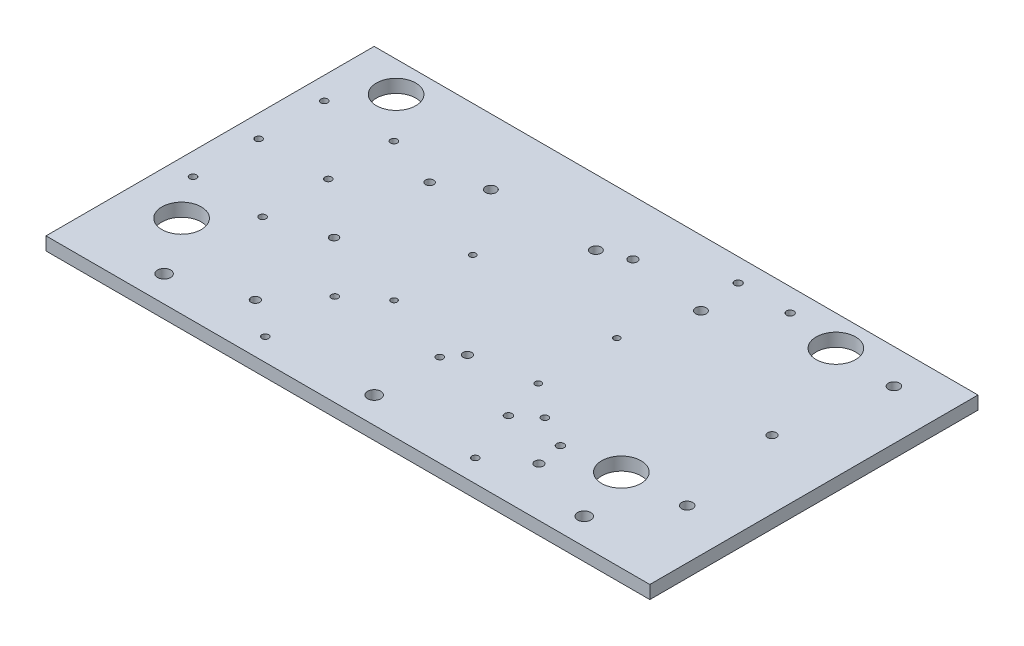
SolidWorks part; units mm, degrees
ref_plane "Front Plane" through (0, 0, 0) normal (0, 0, 1) x (1, 0, 0)
ref_plane "Top Plane" through (0, 0, 0) normal (0, 1, 0) x (1, 0, 0)
ref_plane "Right Plane" through (0, 0, 0) normal (1, 0, 0) x (0, 0, -1)
sketch "Sketch1" plane through (0, 0, 0) normal (0, 1, 0) x (1, 0, 0)
  line L1 (0, 0) -> (292.1, 0)
  line L2 (0, 0) -> (0, 158.75)
  line L3 (0, 158.75) -> (292.1, 158.75)
  line L4 (292.1, 0) -> (292.1, 158.75)
  dimension "D1" = 292.1
  dimension "D2" = 158.75
extrude "Boss-Extrude1" add sketch "Sketch1" along normal blind 6.35
sketch "Sketch2" plane through (0, 6.35, 0) normal (0, 1, 0) x (1, 0, 0)
  line L0 (0, 25.4) -> (292.1, 25.4) construction
  line L1 (0, 12.7) -> (292.1, 12.7) construction
  line L2 (146.05, 0) -> (146.05, 158.75) construction
  line L4 (0, 158.75) -> (0, 0)
  line L5 (0, 0) -> (292.1, 0)
  line L6 (292.1, 0) -> (292.1, 158.75)
  line L7 (292.1, 158.75) -> (0, 158.75)
  line L8 (0, 158.75) -> (0, 0) construction
  line L9 (0, 0) -> (292.1, 0) construction
  line L10 (292.1, 0) -> (292.1, 158.75) construction
  line L11 (292.1, 158.75) -> (0, 158.75) construction
  circle A0 centre (146.05, 12.7) radius 3.175
  circle A1 centre (247.65, 12.7) radius 3.175
  circle A2 centre (44.45, 12.7) radius 3.175
  dimension "D6" = 6.35
  dimension "D7" = 6.35
  dimension "D8" = 6.35
  dimension "D2" = 25.4
  dimension "D3" = 12.7
  dimension "D4" = 101.6
  dimension "D5" = 101.6
extrude "Cut-Extrude2" cut sketch "Sketch2" against normal blind 6.35
sketch "Sketch5" [suppressed] plane through (0, 6.35, 0) normal (0, 1, 0) x (1, 0, 0)
  line L0 (0, 0) -> (292.1, 0) construction
  line L1 (279.4, 31.75) -> (143.9, 31.75) construction
  line L2 (279.4, 31.75) -> (279.4, 75.25) construction
  line L3 (279.4, 75.25) -> (143.9, 75.25) construction
  line L4 (143.9, 31.75) -> (143.9, 75.25) construction
  line L5 (292.1, 0) -> (292.1, 158.75) construction
  circle A0 centre (279.4, 31.75) radius 1.525
  circle A1 centre (279.4, 75.25) radius 1.525
  circle A2 centre (143.9, 75.25) radius 1.525
  circle A3 centre (143.9, 31.75) radius 1.525
  dimension "D3" = 3.05
  dimension "D1" = 43.5
  dimension "D2" = 135.5
  dimension "D4" = 31.75
  dimension "D5" = 12.7
sketch "Sketch6" plane through (0, 6.35, 0) normal (0, 1, 0) x (1, 0, 0)
  line L0 (238.125, 158.75) -> (238.125, 0) construction
  line L1 (292.1, 158.75) -> (0, 158.75) construction
  line L2 (0, 0) -> (292.1, 0) construction
  line L4 (146.05, 158.75) -> (146.05, 0) construction
  line L5 (0, 25.4) -> (292.1, 25.4) construction
  line L6 (0, 158.75) -> (0, 0) construction
  line L7 (292.1, 0) -> (292.1, 158.75) construction
  line L8 (25.4, 40.1879) -> (238.125, 40.1879) construction
  line L9 (25.4, 143.9621) -> (238.125, 143.9621) construction
  line L10 (0, 92.075) -> (292.1, 92.075) construction
  line L11 (0, 158.75) -> (0, 25.4) construction
  line L12 (25.4, 143.9621) -> (25.4, 92.075) construction
  line L13 (25.4, 92.075) -> (25.4, 40.1879) construction
  circle A0 centre (25.4, 40.1879) radius 9.525
  circle A1 centre (238.125, 40.1879) radius 9.525
  circle A2 centre (25.4, 143.9621) radius 9.525
  circle A3 centre (238.125, 143.9621) radius 9.525
  dimension "D2" = 19.05
  dimension "D3" = 19.05
  dimension "D1" = 25.4
  dimension "D4" = 25.4
  dimension "D5" = 53.975
extrude "Cut-Extrude3" cut sketch "Sketch6" against normal through all
sketch "Sketch8" plane through (0, 6.35, 0) normal (0, 1, 0) x (1, 0, 0)
  line L0 (265.43, 121.908) -> (265.43, 112.242) construction
  line L1 (270.764, 112.242) -> (270.764, 121.908) construction
  line L2 (265.43, 96.908) -> (265.43, 87.242)
  line L3 (270.764, 87.242) -> (270.764, 96.908)
  line L4 (265.43, 96.908) -> (265.43, 87.242) construction
  line L5 (270.764, 87.242) -> (270.764, 96.908) construction
  line L6 (265.43, 146.908) -> (265.43, 137.242) construction
  line L7 (270.764, 137.242) -> (270.764, 146.908) construction
  line L8 (265.43, 96.908) -> (265.43, 87.242) construction
  line L9 (270.764, 87.242) -> (270.764, 96.908) construction
  line L10 (265.43, 121.908) -> (265.43, 112.242) construction
  line L11 (270.764, 112.242) -> (270.764, 121.908) construction
  line L12 (265.43, 71.908) -> (265.43, 62.242) construction
  line L13 (270.764, 62.242) -> (270.764, 71.908) construction
  line L14 (265.43, 96.908) -> (265.43, 87.242) construction
  line L15 (270.764, 87.242) -> (270.764, 96.908) construction
  line L16 (265.43, 71.908) -> (265.43, 62.242) construction
  line L17 (270.764, 62.242) -> (270.764, 71.908) construction
  line L18 (265.43, 46.908) -> (265.43, 37.242) construction
  line L19 (270.764, 37.242) -> (270.764, 46.908) construction
  line L20 (265.43, 96.908) -> (265.43, 121.908) construction
  line L21 (268.097, 137.242) -> (268.097, 146.908) construction
  line L22 (268.097, 37.242) -> (268.097, 46.908) construction
  line L23 (143.764, 129.54) -> (134.239, 129.54) construction
  line L24 (134.239, 124.46) -> (143.764, 124.46) construction
  line L25 (213.1283, 38.3159) -> (211.5027, 38.3159)
  line L26 (211.5027, 34.7345) -> (213.1283, 34.7345)
  line L27 (222.285, 31.6611) -> (222.285, 152.4889)
  line L28 (222.285, 152.4889) -> (177.2, 152.4889)
  line L29 (177.2, 152.4889) -> (177.2, 31.6611)
  line L30 (177.2, 31.6611) -> (222.285, 31.6611)
  line L31 (222.285, 31.6611) -> (222.285, 152.4889) construction
  line L32 (222.285, 152.4889) -> (177.2, 152.4889) construction
  line L33 (177.2, 152.4889) -> (177.2, 31.6611) construction
  line L34 (177.2, 31.6611) -> (222.285, 31.6611) construction
  line L35 (213.1283, 38.3159) -> (211.5027, 38.3159) construction
  line L36 (211.5027, 34.7345) -> (213.1283, 34.7345) construction
  line L37 (187.9823, 38.3159) -> (186.3567, 38.3159)
  line L38 (186.3567, 34.7345) -> (187.9823, 34.7345)
  line L39 (187.9823, 38.3159) -> (186.3567, 38.3159) construction
  line L40 (186.3567, 34.7345) -> (187.9823, 34.7345) construction
  line L41 (211.5027, 145.8341) -> (213.1283, 145.8341)
  line L42 (213.1283, 149.4155) -> (211.5027, 149.4155)
  line L43 (211.5027, 145.8341) -> (213.1283, 145.8341) construction
  line L44 (213.1283, 149.4155) -> (211.5027, 149.4155) construction
  line L45 (186.3567, 145.8341) -> (187.9823, 145.8341)
  line L46 (187.9823, 149.4155) -> (186.3567, 149.4155)
  line L47 (186.3567, 145.8341) -> (187.9823, 145.8341) construction
  line L48 (187.9823, 149.4155) -> (186.3567, 149.4155) construction
  line L49 (194.564, 129.54) -> (185.039, 129.54)
  line L50 (185.039, 124.46) -> (194.564, 124.46)
  line L51 (194.564, 129.54) -> (185.039, 129.54) construction
  line L52 (185.039, 124.46) -> (194.564, 124.46) construction
  line L53 (92.964, 129.54) -> (83.439, 129.54) construction
  line L54 (83.439, 124.46) -> (92.964, 124.46) construction
  line L55 (194.564, 129.54) -> (143.764, 129.54) construction
  line L56 (83.439, 127) -> (194.564, 127) construction
  line L57 (189.8015, 124.46) -> (189.8015, 129.54) construction
  line L58 (88.2015, 124.46) -> (88.2015, 129.54) construction
  line L63 (109.05, 54.7) -> (183.05, 54.7)
  line L64 (183.05, 54.7) -> (183.05, 97.7)
  line L65 (183.05, 97.7) -> (109.05, 97.7)
  line L66 (109.05, 97.7) -> (109.05, 54.7)
  line L67 (109.05, 54.7) -> (183.05, 54.7) construction
  line L68 (183.05, 54.7) -> (183.05, 97.7) construction
  line L69 (183.05, 97.7) -> (109.05, 97.7) construction
  line L70 (109.05, 97.7) -> (109.05, 54.7) construction
  line L82 (186.3567, 36.5252) -> (187.9823, 36.5252) construction
  line L83 (211.5027, 36.5252) -> (213.1283, 36.5252) construction
  line L84 (211.5027, 147.6248) -> (213.1283, 147.6248) construction
  line L85 (186.3567, 147.6248) -> (187.9823, 147.6248) construction
  line L88 (70.3882, 66.9707) -> (81.4118, 66.9707)
  line L89 (81.4118, 70.9077) -> (70.3882, 70.9077)
  line L90 (70.3882, 66.9707) -> (81.4118, 66.9707) construction
  line L91 (81.4118, 70.9077) -> (70.3882, 70.9077) construction
  line L92 (77.8685, 63.0845) -> (77.8685, 68.9392)
  line L93 (73.9315, 68.9392) -> (73.9315, 63.0845)
  line L94 (126.4, 44.9707) -> (126.4, 139.1793)
  line L95 (25.4, 44.9707) -> (126.4, 44.9707)
  line L96 (25.4, 139.1793) -> (25.4, 44.9707)
  line L97 (126.4, 139.1793) -> (25.4, 139.1793)
  line L98 (126.4, 44.9707) -> (126.4, 139.1793) construction
  line L99 (25.4, 44.9707) -> (126.4, 44.9707) construction
  line L100 (25.4, 139.1793) -> (25.4, 44.9707) construction
  line L101 (126.4, 139.1793) -> (25.4, 139.1793) construction
  line L102 (77.8685, 63.0845) -> (77.8685, 68.9392) construction
  line L103 (73.9315, 68.9392) -> (73.9315, 63.0845) construction
  line L104 (73.9315, 115.2108) -> (73.9315, 109.3561)
  line L105 (77.8685, 109.3561) -> (77.8685, 115.2108)
  line L106 (73.9315, 115.2108) -> (73.9315, 109.3561) construction
  line L107 (77.8685, 109.3561) -> (77.8685, 115.2108) construction
  line L108 (70.3882, 113.2423) -> (81.4118, 113.2423)
  line L109 (81.4118, 117.1793) -> (70.3882, 117.1793)
  line L110 (70.3882, 113.2423) -> (81.4118, 113.2423) construction
  line L111 (81.4118, 117.1793) -> (70.3882, 117.1793) construction
  arc A0 (265.43, 112.242) -> (270.764, 112.242) centre (268.097, 112.242) ccw construction
  arc A1 (270.764, 121.908) -> (265.43, 121.908) centre (268.097, 121.908) ccw construction
  arc A2 (265.43, 87.242) -> (270.764, 87.242) centre (268.097, 87.242) ccw
  arc A3 (270.764, 96.908) -> (265.43, 96.908) centre (268.097, 96.908) ccw
  arc A4 (265.43, 87.242) -> (270.764, 87.242) centre (268.097, 87.242) ccw construction
  arc A5 (270.764, 96.908) -> (265.43, 96.908) centre (268.097, 96.908) ccw construction
  arc A6 (265.43, 137.242) -> (270.764, 137.242) centre (268.097, 137.242) ccw construction
  arc A7 (270.764, 146.908) -> (265.43, 146.908) centre (268.097, 146.908) ccw construction
  arc A8 (265.43, 87.242) -> (270.764, 87.242) centre (268.097, 87.242) ccw construction
  arc A9 (270.764, 96.908) -> (265.43, 96.908) centre (268.097, 96.908) ccw construction
  arc A10 (265.43, 112.242) -> (270.764, 112.242) centre (268.097, 112.242) ccw construction
  arc A11 (270.764, 121.908) -> (265.43, 121.908) centre (268.097, 121.908) ccw construction
  arc A12 (265.43, 62.242) -> (270.764, 62.242) centre (268.097, 62.242) ccw construction
  arc A13 (270.764, 71.908) -> (265.43, 71.908) centre (268.097, 71.908) ccw construction
  arc A14 (265.43, 87.242) -> (270.764, 87.242) centre (268.097, 87.242) ccw construction
  arc A15 (270.764, 96.908) -> (265.43, 96.908) centre (268.097, 96.908) ccw construction
  arc A16 (265.43, 62.242) -> (270.764, 62.242) centre (268.097, 62.242) ccw construction
  arc A17 (270.764, 71.908) -> (265.43, 71.908) centre (268.097, 71.908) ccw construction
  arc A18 (265.43, 37.242) -> (270.764, 37.242) centre (268.097, 37.242) ccw construction
  arc A19 (270.764, 46.908) -> (265.43, 46.908) centre (268.097, 46.908) ccw construction
  circle A20 centre (268.097, 42.075) radius 2.667
  circle A21 centre (268.097, 142.075) radius 2.667
  arc A22 (134.239, 129.54) -> (134.239, 124.46) centre (134.239, 127) ccw construction
  arc A23 (143.764, 124.46) -> (143.764, 129.54) centre (143.764, 127) ccw construction
  arc A24 (211.5027, 38.3159) -> (211.5027, 34.7345) centre (211.5027, 36.5252) ccw
  arc A25 (213.1283, 34.7345) -> (213.1283, 38.3159) centre (213.1283, 36.5252) ccw
  arc A26 (211.5027, 38.3159) -> (211.5027, 34.7345) centre (211.5027, 36.5252) ccw construction
  arc A27 (213.1283, 34.7345) -> (213.1283, 38.3159) centre (213.1283, 36.5252) ccw construction
  arc A28 (187.9823, 34.7345) -> (187.9823, 38.3159) centre (187.9823, 36.5252) ccw
  arc A29 (186.3567, 38.3159) -> (186.3567, 34.7345) centre (186.3567, 36.5252) ccw
  arc A30 (187.9823, 34.7345) -> (187.9823, 38.3159) centre (187.9823, 36.5252) ccw construction
  arc A31 (186.3567, 38.3159) -> (186.3567, 34.7345) centre (186.3567, 36.5252) ccw construction
  arc A32 (211.5027, 149.4155) -> (211.5027, 145.8341) centre (211.5027, 147.6248) ccw
  arc A33 (213.1283, 145.8341) -> (213.1283, 149.4155) centre (213.1283, 147.6248) ccw
  arc A34 (211.5027, 149.4155) -> (211.5027, 145.8341) centre (211.5027, 147.6248) ccw construction
  arc A35 (213.1283, 145.8341) -> (213.1283, 149.4155) centre (213.1283, 147.6248) ccw construction
  arc A36 (187.9823, 145.8341) -> (187.9823, 149.4155) centre (187.9823, 147.6248) ccw
  arc A37 (186.3567, 149.4155) -> (186.3567, 145.8341) centre (186.3567, 147.6248) ccw
  arc A38 (187.9823, 145.8341) -> (187.9823, 149.4155) centre (187.9823, 147.6248) ccw construction
  arc A39 (186.3567, 149.4155) -> (186.3567, 145.8341) centre (186.3567, 147.6248) ccw construction
  arc A40 (185.039, 129.54) -> (185.039, 124.46) centre (185.039, 127) ccw
  arc A41 (194.564, 124.46) -> (194.564, 129.54) centre (194.564, 127) ccw
  arc A42 (185.039, 129.54) -> (185.039, 124.46) centre (185.039, 127) ccw construction
  arc A43 (194.564, 124.46) -> (194.564, 129.54) centre (194.564, 127) ccw construction
  arc A44 (83.439, 129.54) -> (83.439, 124.46) centre (83.439, 127) ccw construction
  arc A45 (92.964, 124.46) -> (92.964, 129.54) centre (92.964, 127) ccw construction
  circle A46 centre (189.8015, 127) radius 2.54
  circle A47 centre (139.0015, 127) radius 2.54
  circle A48 centre (88.2015, 127) radius 2.54
  circle A50 centre (111.2, 57.2) radius 1.5
  circle A51 centre (111.2, 57.2) radius 1.5
  circle A52 centre (180.9, 57.2) radius 1.5
  circle A53 centre (180.9, 57.2) radius 1.5
  circle A54 centre (180.9, 95.2) radius 1.5
  circle A55 centre (180.9, 95.2) radius 1.5
  circle A56 centre (111.2, 95.2) radius 1.5
  circle A57 centre (111.2, 95.2) radius 1.5
  circle A58 centre (95.25, 10.795) radius 1.651
  circle A59 centre (95.25, 10.795) radius 1.651
  circle A60 centre (196.85, 10.795) radius 1.651
  circle A61 centre (196.85, 10.795) radius 1.651
  circle A62 centre (196.85, 44.45) radius 1.651
  circle A63 centre (196.85, 44.45) radius 1.651
  circle A64 centre (95.25, 44.45) radius 1.651
  circle A65 centre (95.25, 44.45) radius 1.651
  circle A66 centre (10.795, 123.825) radius 1.651
  circle A67 centre (10.795, 123.825) radius 1.651
  circle A68 centre (10.795, 60.325) radius 1.651
  circle A69 centre (10.795, 60.325) radius 1.651
  circle A70 centre (44.45, 60.325) radius 1.651
  circle A71 centre (44.45, 60.325) radius 1.651
  circle A72 centre (44.45, 123.825) radius 1.651
  circle A73 centre (44.45, 123.825) radius 1.651
  circle A74 centre (77.451, 23.8125) radius 2.0955
  circle A75 centre (77.451, 23.8125) radius 2.0955
  circle A77 centre (151.8, 132.099) radius 2.0955
  circle A78 centre (151.8, 132.099) radius 2.0955
  circle A80 centre (214.649, 23.8125) radius 2.0955
  circle A81 centre (214.649, 23.8125) radius 2.0955
  circle A83 centre (151.8, 52.051) radius 2.0955
  circle A84 centre (151.8, 52.051) radius 2.0955
  circle A86 centre (259.099, 92.075) radius 2.0955
  circle A87 centre (259.099, 92.075) radius 2.0955
  circle A88 centre (187.1695, 36.5252) radius 1.7907
  circle A89 centre (212.3155, 36.5252) radius 1.7907
  circle A90 centre (212.3155, 147.6248) radius 1.7907
  circle A91 centre (187.1695, 147.6248) radius 1.7907
  circle A92 centre (70.3882, 115.2108) radius 1.9685
  circle A93 centre (75.9, 68.9392) radius 3.3274
  circle A94 centre (75.9, 68.9392) radius 3.3274 construction
  circle A95 centre (75.9, 115.2108) radius 3.3274
  arc A96 (81.4118, 66.9707) -> (81.4118, 70.9077) centre (81.4118, 68.9392) ccw
  arc A97 (70.3882, 70.9077) -> (70.3882, 66.9707) centre (70.3882, 68.9392) ccw
  arc A98 (81.4118, 66.9707) -> (81.4118, 70.9077) centre (81.4118, 68.9392) ccw construction
  arc A99 (70.3882, 70.9077) -> (70.3882, 66.9707) centre (70.3882, 68.9392) ccw construction
  arc A100 (73.9315, 63.0845) -> (77.8685, 63.0845) centre (75.9, 63.0845) ccw
  arc A101 (77.8685, 68.9392) -> (73.9315, 68.9392) centre (75.9, 68.9392) ccw
  arc A102 (73.9315, 63.0845) -> (77.8685, 63.0845) centre (75.9, 63.0845) ccw construction
  arc A103 (77.8685, 68.9392) -> (73.9315, 68.9392) centre (75.9, 68.9392) ccw construction
  circle A104 centre (75.9, 115.2108) radius 3.3274 construction
  circle A105 centre (70.3882, 68.9392) radius 1.9685
  arc A106 (73.9315, 109.3561) -> (77.8685, 109.3561) centre (75.9, 109.3561) ccw
  arc A107 (77.8685, 115.2108) -> (73.9315, 115.2108) centre (75.9, 115.2108) ccw
  arc A108 (73.9315, 109.3561) -> (77.8685, 109.3561) centre (75.9, 109.3561) ccw construction
  arc A109 (77.8685, 115.2108) -> (73.9315, 115.2108) centre (75.9, 115.2108) ccw construction
  arc A110 (81.4118, 113.2423) -> (81.4118, 117.1793) centre (81.4118, 115.2108) ccw
  arc A111 (70.3882, 117.1793) -> (70.3882, 113.2423) centre (70.3882, 115.2108) ccw
  arc A112 (81.4118, 113.2423) -> (81.4118, 117.1793) centre (81.4118, 115.2108) ccw construction
  arc A113 (70.3882, 117.1793) -> (70.3882, 113.2423) centre (70.3882, 115.2108) ccw construction
  circle A121 centre (44.45, 92.075) radius 1.651 construction
  circle A122 centre (10.795, 92.075) radius 1.651 construction
  circle A123 centre (44.45, 92.075) radius 1.651
  circle A124 centre (10.795, 92.075) radius 1.651
  circle A129 centre (146.05, 44.45) radius 1.651 construction
  circle A130 centre (146.05, 44.45) radius 1.651
  dimension "D4" = 25
  dimension "D12" = 50.8
  dimension "D1" = 0
  dimension "D5" = 0
  dimension "D6" = 0
  dimension "D7" = 0
  dimension "D8" = 0
  dimension "D9" = 0
  dimension "D10" = 0
  dimension "D13" = 0
  dimension "D14" = 0
  dimension "D15" = 0
  dimension "D16" = 0
  dimension "D17" = 0
  dimension "D18" = 0
  dimension "D19" = 0
  dimension "D20" = 0
  dimension "D21" = 0
  dimension "D22" = 0
  dimension "D23" = 0
  dimension "D24" = 0
  dimension "D25" = 0
  dimension "D26" = 0
  dimension "D27" = 0
  dimension "D28" = 0
  dimension "D29" = 0
  dimension "D30" = 0
  dimension "D31" = 0
  dimension "D32" = 0
  dimension "D33" = 0
  dimension "D34" = 0
  dimension "D35" = 0
  dimension "D36" = 0
  dimension "D37" = 0
  dimension "D2" = 3
  dimension "D3" = 3
  dimension "D11" = 3
extrude "Cut-Extrude4" cut sketch "Sketch8" against normal through all
equation "\"D5@Sketch2\"=\"D4@Sketch2\""
equation "\"D7@Sketch2\"=\"D6@Sketch2\""
equation "\"D8@Sketch2\"=\"D7@Sketch2\""
equation "\"D4@Sketch5\"=1.25*25.4"
